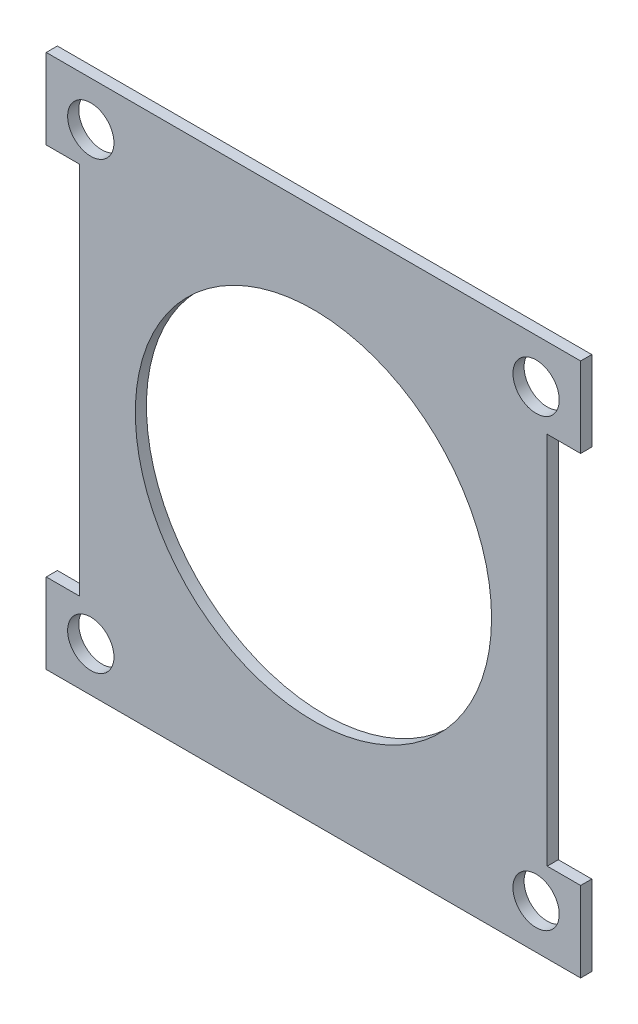
SolidWorks part; units mm, degrees
ref_plane "Front Plane" through (0, 0, 0) normal (0, 0, 1) x (1, 0, 0)
ref_plane "Top Plane" through (0, 0, 0) normal (0, 1, 0) x (1, 0, 0)
ref_plane "Right Plane" through (0, 0, 0) normal (1, 0, 0) x (0, 0, -1)
sketch "Sketch1" plane through (0, 0, 0) normal (0, 0, 1) x (1, 0, 0)
  line L1 (-38.1, 38.1) -> (38.1, 38.1)
  line L2 (-38.1, 38.1) -> (-38.1, -38.1)
  line L3 (-38.1, -38.1) -> (38.1, -38.1)
  line L4 (38.1, 38.1) -> (38.1, -38.1)
  circle A0 centre (0, 0) radius 25.4
  dimension "D5" = 50.8
  dimension "D1" = 76.2
  dimension "D2" = 76.2
  dimension "D3" = 38.1
  dimension "D4" = 38.1
extrude "Boss-Extrude1" add sketch "Sketch1" along normal blind 1.5875
sketch "Sketch2" plane through (0, 0, 1.5875) normal (0, 0, 1) x (1, 0, 0)
  line L0 (0, 25.7973) -> (0, -24.2806) construction
  line L1 (-23.5201, 0) -> (29.7887, 0) construction
  line L2 (0, 0) -> (-59.488, 59.488) construction
  circle A0 centre (-31.75, 31.75) radius 3.302
  dimension "D3" = 6.604
  dimension "D1" = 45
  dimension "D2" = 31.75
extrude "Cut-Extrude1" cut sketch "Sketch2" against normal blind 3.175
mirror "Mirror1" about plane through (0, 0, 0) normal (1, 0, 0) of "Cut-Extrude1"
mirror "Mirror2" about plane through (0, 0, 0) normal (0, 1, 0) of "Mirror1"
sketch "Sketch3" plane through (0, 0, 1.5875) normal (0, 0, 1) x (1, 0, 0)
  circle A0 centre (0, 0) radius 31.75
  circle A1 centre (0, 0) radius 25.4
  dimension "D1" = 50.8
  dimension "D2" = 6.35
extrude "Boss-Extrude2" [suppressed] add sketch "Sketch3" along normal blind 0.508 and the other way blind 3.683
sketch "Sketch4" plane through (0, 0, 1.5875) normal (0, 0, 1) x (1, 0, 0)
  line L0 (0, 0) -> (0, 68.7637) construction
  line L1 (0, 0) -> (-65.8141, 0) construction
  line L2 (0, 0) -> (-65.1608, 37.6206) construction
  circle A0 centre (-32.9956, 19.05) radius 2.6363
  dimension "D1" = 30
  dimension "D2" = 38.1
extrude "Cut-Extrude2" [suppressed] cut sketch "Sketch4" against normal through all
pattern_circular "CirPattern1" [suppressed] count 3 over 360 of bodies 104
sketch "Sketch5" [suppressed] plane through (0, 0, 3.175) normal (0, 0, 1) x (1, 0, 0)
  line L0 (38.1, 38.1) -> (-38.1, 38.1) construction
  line L1 (-32.5317, 43.1268) -> (-32.5317, 43.8308)
  line L2 (-33.655, 42.542) -> (-33.655, 43.8308)
  line L3 (27.9712, 43.8308) -> (26.8595, 43.8308)
  line L4 (-33.655, 43.8308) -> (-34.7667, 43.8308)
  line L5 (0, 0) -> (0, 22.3546) construction
  line L6 (26.8595, 43.8308) -> (26.8595, 38.1)
  line L7 (-34.7667, 43.8308) -> (-34.7667, 38.1)
  line L8 (26.8595, 38.1) -> (29.7358, 38.1)
  line L9 (-34.7667, 38.1) -> (-31.42, 38.1)
  line L10 (27.9712, 43.8308) -> (27.9712, 43.1268)
  line L11 (-33.655, 42.542) -> (28.112, 42.542)
  line L12 (29.7358, 38.1) -> (29.7358, 43.8308)
  line L13 (-31.42, 38.1) -> (-31.42, 43.8308)
  line L14 (29.7358, 43.8308) -> (28.6241, 43.8308)
  line L15 (-31.42, 43.8308) -> (-32.5317, 43.8308)
  line L16 (28.6241, 43.8308) -> (28.6241, 18.7448)
  line L17 (28.112, 42.542) -> (25.626, 18.7448)
  line L18 (27.9712, 43.1268) -> (-32.5317, 43.1268)
  line L19 (25.626, 18.7448) -> (28.6241, 18.7448)
  circle A1 centre (0, 0) radius 31.75 construction
  dimension "D1" = 1.2888
  dimension "D2" = 0.704
extrude "Boss-Extrude3" [suppressed] add sketch "Sketch5" along normal blind 0.3175
sketch "Sketch7" [suppressed] plane through (0, 0, 0) normal (0, 0, -1) x (-1, 0, 0)
  line L0 (14.2714, 32.8184) -> (14.2714, 28.3618)
  line L1 (13.6364, 34.129) -> (13.6364, 28.6725)
  line L2 (14.2714, 28.3618) -> (13.6364, 28.6725)
  line L3 (-38.1, 38.1) -> (38.1, 38.1) construction
  line L4 (38.1, 38.1) -> (38.1, -38.1) construction
  arc A0 (14.2714, 32.8184) -> (13.6364, 34.129) centre (13.0175, 33.02) ccw
  circle A1 centre (0, 0) radius 31.75 construction
  dimension "D4" = 1.27
  dimension "D3" = 5.08
  dimension "D1" = 25.0825
  dimension "D2" = 0.635
extrude "Boss-Extrude4" [suppressed] add sketch "Sketch7" along normal blind 0.3175
sketch "Sketch8" plane through (0, 0, 1.5875) normal (0, 0, 1) x (1, 0, 0)
  line L0 (-32.0415, 38.1) -> (-29.5015, 38.1)
  line L1 (38.1, 38.1) -> (-38.1, 38.1) construction
  line L2 (-32.0415, 38.1) -> (-32.0415, 37.592)
  line L3 (-32.0415, 37.592) -> (-31.0255, 37.592)
  line L4 (-29.5015, 38.1) -> (-29.5015, 37.592)
  line L5 (-29.5015, 37.592) -> (-30.5175, 37.592)
  line L6 (-31.0255, 37.592) -> (-31.0255, 36.322)
  line L7 (-30.5175, 37.592) -> (-30.5175, 36.83)
  line L8 (-31.0255, 36.322) -> (24.0382, 36.322)
  line L9 (24.0382, 36.322) -> (24.0382, 25.5685)
  line L10 (-30.5175, 36.83) -> (24.0382, 36.83)
  line L11 (24.0382, 36.83) -> (24.0382, 37.592)
  line L12 (24.0382, 37.592) -> (23.0222, 37.592)
  line L13 (23.0222, 37.592) -> (23.0222, 38.1)
  line L14 (23.0222, 38.1) -> (25.5622, 38.1)
  line L15 (25.5622, 38.1) -> (25.5622, 37.592)
  line L16 (25.5622, 37.592) -> (24.5462, 37.592)
  line L17 (24.5462, 37.592) -> (24.5462, 25.5685)
  line L18 (24.5462, 25.5685) -> (24.0382, 25.5685)
  dimension "D1" = 1.27
  dimension "D2" = 0.762
  dimension "D3" = 0.508
  dimension "D4" = 0.508
  dimension "D5" = 0.508
  dimension "D6" = 2.54
  dimension "D7" = 0.762
  dimension "D8" = 0.508
  dimension "D9" = 2.54
extrude "Boss-Extrude10" [suppressed] add sketch "Sketch8" along normal blind 0.3175
sketch "Sketch9" plane through (0, 0, 1.5875) normal (0, 0, 1) x (1, 0, 0)
  line L0 (-38.1, 38.1) -> (-38.1, -38.1) construction
  line L1 (-38.1, 26.67) -> (-33.3375, 26.67)
  line L2 (-38.1, 26.67) -> (-38.1, -26.67)
  line L3 (-38.1, -26.67) -> (-33.3375, -26.67)
  line L4 (-33.3375, 26.67) -> (-33.3375, -26.67)
  dimension "D1" = 53.34
  dimension "D2" = 26.67
  dimension "D3" = 4.7625
extrude "Cut-Extrude3" cut sketch "Sketch9" against normal through all
mirror "Mirror3" about plane through (0, 0, 0) normal (1, 0, 0) of "Cut-Extrude3"
equation "\"D4@Sketch1\"=\"D1@Sketch1\"/2"
equation "\"D3@Sketch1\"=\"D2@Sketch1\"/2"
equation "\"D1@Sketch3\"=\"D5@Sketch1\""
equation "\"D2@Sketch9\"=\"D1@Sketch9\"/2"
